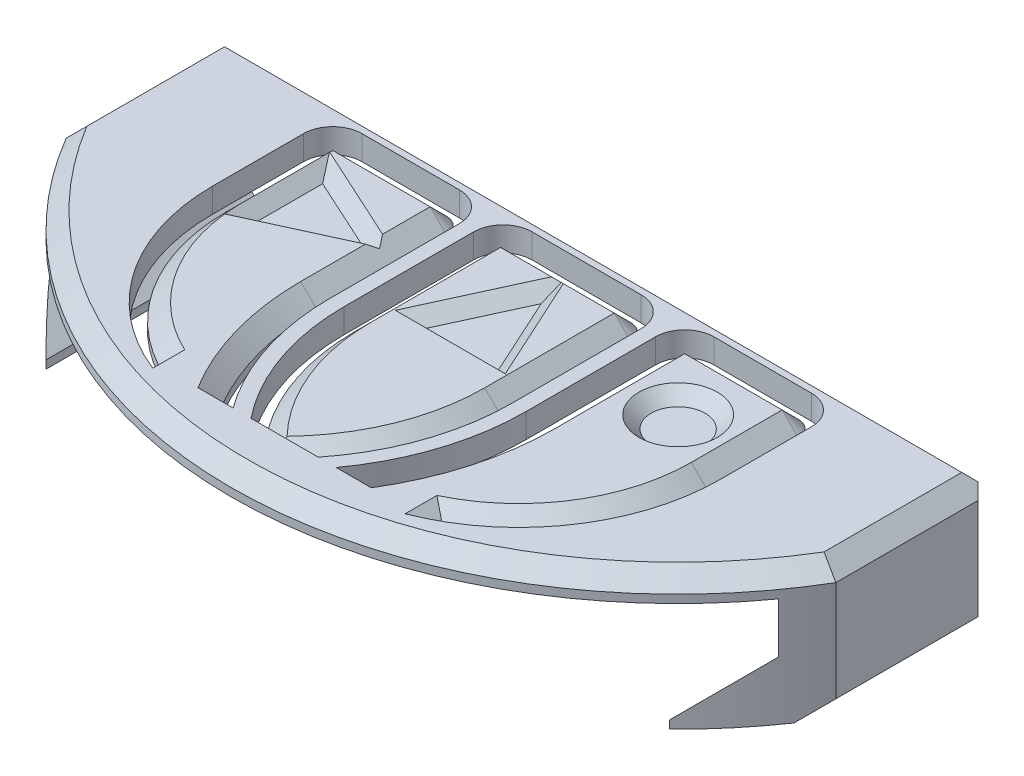
SolidWorks part; units mm, degrees
ref_plane "Front Plane" through (0, 0, 0) normal (0, 0, 1) x (1, 0, 0)
ref_plane "Top Plane" through (0, 0, 0) normal (0, 1, 0) x (1, 0, 0)
ref_plane "Right Plane" through (0, 0, 0) normal (1, 0, 0) x (0, 0, -1)
sketch "Sketch1" plane through (0, 0, 0) normal (0, 1, 0) x (1, 0, 0)
  line L20 (-19.2, 7.5) -> (-19.2, -7.9922)
  line L21 (19.2, 7.5) -> (19.2, -7.9922)
  line L29 (-4.5, -3.6738) -> (-4.5, 4.3)
  line L30 (-3.5, 5.3) -> (3.5, 5.3)
  line L31 (4.5, -3.6738) -> (4.5, 4.3)
  line L32 (-15.6377, 4.3) -> (-15.6377, -1.291)
  line L33 (-13.8377, 6.1) -> (-7.8377, 6.1) construction
  line L35 (6.8377, -3.6738) -> (6.8377, 4.3)
  line L36 (7.8377, 5.3) -> (13.8377, 5.3)
  line L37 (14.8377, -1.291) -> (14.8377, 4.3)
  line L41 (-14.8377, -1.291) -> (-14.8377, 4.3)
  line L42 (-13.8377, 5.3) -> (-7.8377, 5.3)
  line L43 (-6.8377, -3.6738) -> (-6.8377, 4.3)
  line L46 (-2.8, -11.5) -> (-2, -11.5)
  line L47 (-5.1594, -3.6738) -> (-5.1594, 4.3)
  line L48 (-3.3594, 6.1) -> (3.3594, 6.1) construction
  line L49 (5.1594, -3.6738) -> (5.1594, 4.3)
  line L50 (2.8, -11.5) -> (2, -11.5)
  line L51 (-6.0377, 4.3) -> (-6.0377, -3.6738)
  line L52 (15.6377, -1.291) -> (15.6377, 4.3)
  line L53 (13.8377, 6.1) -> (7.8377, 6.1) construction
  line L54 (6.0377, 4.3) -> (6.0377, -3.6738)
  line L55 (-8.7689, -11.5) -> (-8.7689, -12.4022)
  line L56 (-4.7689, -11.5) -> (-3.8406, -11.5)
  line L57 (3.8406, -11.5) -> (4.7689, -11.5)
  line L58 (8.7689, -11.5) -> (8.7689, -12.4022)
  line L65 (-23.7, 7.5) -> (23.7, 7.5)
  line L66 (-23.7, 7.5) -> (-23.7, -2.2528)
  line L68 (23.7, 7.5) -> (23.7, -2.2528)
  line L87 (-13.8377, 6.1) -> (-7.8377, 6.1)
  line L88 (-3.3594, 6.1) -> (3.3594, 6.1)
  line L89 (7.8377, 6.1) -> (13.8377, 6.1)
  circle A3 centre (0, 11.6956) radius 25 construction
  circle A4 centre (0, 11.6956) radius 27.5 construction
  arc A5 (-14.8377, -1.291) -> (-8.7689, -11.5) centre (-3.2164, -1.291) ccw
  arc A6 (-6.8377, -3.6738) -> (-4.7689, -11.5) centre (9, -3.6738) ccw
  arc A7 (4.5, -3.6738) -> (2, -11.5) centre (-9, -3.6738) cw
  arc A8 (-4.5, -3.6738) -> (-2, -11.5) centre (9, -3.6738) ccw
  arc A9 (6.8377, -3.6738) -> (4.7689, -11.5) centre (-9, -3.6738) cw
  arc A10 (14.8377, -1.291) -> (8.7689, -11.5) centre (3.2164, -1.291) cw
  arc A11 (4.5, 4.3) -> (3.5, 5.3) centre (3.5, 4.3) ccw
  arc A12 (-3.5, 5.3) -> (-4.5, 4.3) centre (-3.5, 4.3) ccw
  arc A13 (-2.8, -11.5) -> (-5.1594, -3.6738) centre (9, -3.6738) cw
  arc A14 (-3.3594, 6.1) -> (-5.1594, 4.3) centre (-3.3594, 4.3) ccw
  arc A15 (3.3594, 6.1) -> (5.1594, 4.3) centre (3.3594, 4.3) cw
  arc A16 (2.8, -11.5) -> (5.1594, -3.6738) centre (-9, -3.6738) ccw
  arc A17 (-15.6377, -1.291) -> (-8.7689, -12.4022) centre (-3.2164, -1.291) ccw
  arc A18 (-6.0377, -3.6738) -> (-3.8406, -11.5) centre (9, -3.6738) ccw
  arc A19 (6.0377, -3.6738) -> (3.8406, -11.5) centre (-9, -3.6738) cw
  arc A20 (15.6377, -1.291) -> (8.7689, -12.4022) centre (3.2164, -1.291) cw
  arc A21 (-6.8377, 4.3) -> (-7.8377, 5.3) centre (-7.8377, 4.3) ccw
  arc A22 (-13.8377, 5.3) -> (-14.8377, 4.3) centre (-13.8377, 4.3) ccw
  arc A23 (15.6377, 4.3) -> (13.8377, 6.1) centre (13.8377, 4.3) ccw
  arc A24 (7.8377, 6.1) -> (6.0377, 4.3) centre (7.8377, 4.3) ccw
  arc A25 (-6.0377, 4.3) -> (-7.8377, 6.1) centre (-7.8377, 4.3) ccw
  arc A26 (-13.8377, 6.1) -> (-15.6377, 4.3) centre (-13.8377, 4.3) ccw
  arc A27 (14.8377, 4.3) -> (13.8377, 5.3) centre (13.8377, 4.3) ccw
  arc A28 (7.8377, 5.3) -> (6.8377, 4.3) centre (7.8377, 4.3) ccw
  arc A36 (-23.7, -2.2528) -> (23.7, -2.2528) centre (0, 11.6956) ccw
  point P0 (0, 0)
  point P16 (0, -4)
  point P66 (0, 6.1)
  dimension "D11" = 50
  dimension "D18" = 55
  dimension "D20" = 4
  dimension "D21" = 1
  dimension "D24" = 1.8
  dimension "D36" = 1
  dimension "D40" = 1.8
  dimension "D41" = 1
  dimension "D12" = 4.5
  dimension "D13" = 4.5
  dimension "D22" = 0.8
  dimension "D23" = 0.8
  dimension "D25" = 9
  dimension "D26" = 8
  dimension "D31" = 4
  dimension "D32" = 4
  dimension "D33" = 0.8
  dimension "D34" = 0.8
  dimension "D35" = 0.8
  dimension "D37" = 0.8
  dimension "D38" = 0.8
  dimension "D39" = 0.8
  dimension "D42" = 47.4
extrude "Boss-Extrude3" add sketch "Sketch1" along normal blind 1.5 contours L20 A36 L21 L65 L36 A28 L35 A9 L57 A19 L54 A24 L89 A23 L52 A20 L58 A10 L37 A27 A16 L50 A7 L31 A11 L30 A12 L29 A8 L46 A13 L47 A14 L88 A15 L49 A26 L87 A25 L51 A18 L56 A6 L43 A21 L42 A22 L41 | L66 A36 L20 L65 | L21 A36 L68 L65 region at (0, 0, 3.2527) region at (-21.2845, 0, -0.9524) region at (21.2845, 0, -0.9524)
extrude "Boss-Extrude4" add sketch "Sketch1<9>" against normal blind 6.7 contours L66 A36 L20 L65 | L21 A36 L68 L65 region at (-21.2845, 0, -0.9524) region at (21.2845, 0, -0.9524)
sketch "Sketch1<9>" plane through (0, 0, 0) normal (0, 1, 0) x (1, 0, 0) same geometry as "Sketch1"
sketch "Sketch3" plane through (0, 0, -7.5) normal (0, 0, -1) x (-1, 0, 0)
  line L0 (-19.2, -6.2) -> (-22.3, -3.1)
  line L1 (-19.2, -6.7) -> (-19.2, 0) construction
  line L2 (-22.3, -3.1) -> (-22.3, 0)
  line L3 (-22.3, 0) -> (-19.2, 0)
  line L4 (-19.2, 0) -> (-19.2, -6.2)
  line L5 (0, 0) -> (0, 15.5927) construction
  line L6 (19.2, 0) -> (-19.2, 0) construction
  line L7 (-19.2, -6.7) -> (-23.7, -6.7) construction
  line L8 (22.3, 0) -> (19.2, 0)
  line L9 (22.3, -3.1) -> (22.3, 0)
  line L10 (19.2, -6.2) -> (22.3, -3.1)
  line L11 (19.2, 0) -> (19.2, -6.2)
  dimension "D1" = 0.5
  dimension "D2" = 45
  dimension "D3" = 3.1
extrude "Cut-Extrude2" cut sketch "Sketch3" against normal up to next
sketch "Sketch4" plane through (0, 0, -7.5) normal (0, 0, -1) x (-1, 0, 0)
  line L0 (-22.3, -3.1) -> (-22.3, -6.7)
  line L1 (-19.2, -6.7) -> (-23.7, -6.7) construction
  line L2 (-22.3, -6.7) -> (-19.2, -6.7)
  line L3 (-19.2, -6.7) -> (-19.2, -6.2)
  line L4 (-19.2, -6.2) -> (-22.3, -3.1)
  line L5 (22.3, -3.1) -> (22.3, -6.7)
  line L6 (23.7, -6.7) -> (19.2, -6.7) construction
  line L7 (22.3, -6.7) -> (19.2, -6.7)
  line L8 (19.2, -6.7) -> (19.2, -6.2)
  line L9 (19.2, -6.2) -> (22.3, -3.1)
extrude "Cut-Extrude3" cut sketch "Sketch4" against normal blind 1.5
chamfer "Chamfer1" distance 1 angle 45 3 edges at (23.7, 1.5, -2.6236) (0, 1.5, 15.8044) (-23.7, 1.5, -2.6236)
chamfer "Chamfer2" distance 1 angle 45 27 edges at (8.7689, 1.5, 11.9511) (13.2059, 1.5, 7.2293) (14.8377, 1.5, -1.5045) (14.5448, 1.5, -5.0071) (10.8377, 1.5, -5.3) (7.1305, 1.5, -5.0071) (6.8377, 1.5, -0.3131) (6.3117, 1.5, 7.7213) (4.3047, 1.5, 11.5) (2.4, 1.5, 11.5) (3.8598, 1.5, 7.7817) (4.5, 1.5, -0.3131) (4.2071, 1.5, -5.0071) (0, 1.5, -5.3) (-4.2071, 1.5, -5.0071) (-4.5, 1.5, -0.3131) (-3.8598, 1.5, 7.7817) (-2.4, 1.5, 11.5) (-4.3047, 1.5, 11.5) (-6.3117, 1.5, 7.7213) (-6.8377, 1.5, -0.3131) (-7.1305, 1.5, -5.0071) (-10.8377, 1.5, -5.3) (-14.5448, 1.5, -5.0071) (-14.8377, 1.5, -1.5045) (-8.7689, 1.5, 11.9511) (-13.2059, 1.5, 7.2293)
chamfer "Chamfer3" distance 1 angle 45 5 edges at (23.7, -6.7, -2.6236) (23.7, -3.1, -7.5) (0, 1.5, -7.5) (-23.7, -6.7, -2.6236) (-23.7, -3.1, -7.5)
sketch "Sketch5" plane through (0, 1.5, 0) normal (0, 1, 0) x (1, 0, 0)
  line L0 (-13.1267, 2.9674) -> (-13.1267, -1.285)
  line L1 (-13.1267, -1.285) -> (-8.4841, 0.8412)
  line L2 (-8.4841, 0.8412) -> (-13.1267, 2.9674)
  line L3 (0, 3.2971) -> (-2.2187, -1.5473)
  line L4 (-2.2187, -1.5473) -> (2.2187, -1.5473)
  line L5 (2.2187, -1.5473) -> (0, 3.2971)
  line L6 (0, 0) -> (0, 3.2971) construction
  line L7 (-13.1267, 0.8412) -> (-8.4841, 0.8412) construction
  circle A0 centre (10.8935, 0.8412) radius 2.4141
  point P11 (-12.8575, -1.5473)
  point P12 (-8.4841, 0.8412)
  point P13 (0, 3.2971)
  point P14 (10.8935, 0.8412)
extrude "Cut-Extrude4" cut sketch "Sketch5" against normal blind 0.75
chamfer "Chamfer4" distance 0.75 angle 45 7 edges at (-1.1093, 1.5, -0.8749) (0, 1.5, 1.5473) (1.1093, 1.5, -0.8749) (10.8935, 0.75, 1.5728) (-10.8054, 1.5, 0.2219) (-10.8054, 1.5, -1.9043) (-13.1267, 1.5, -0.8412)
